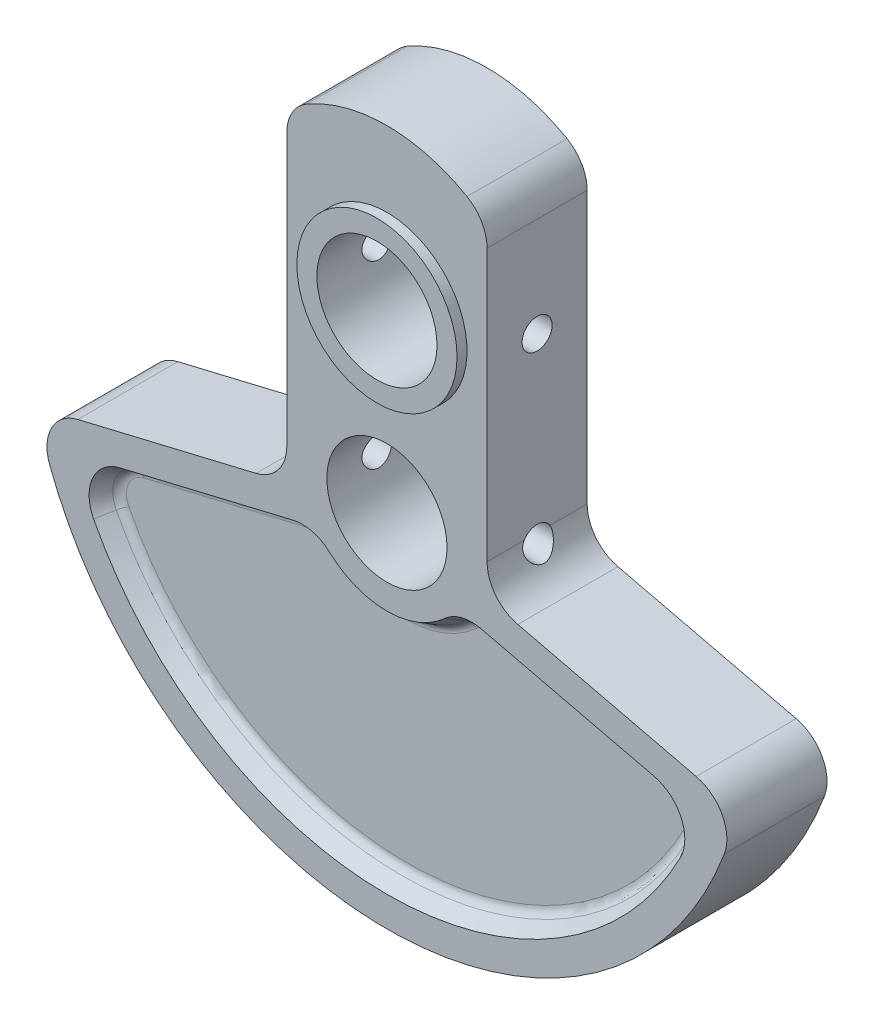
SolidWorks part; units mm, degrees
material "1023 Carbon Steel Sheet (SS)"
ref_plane "Front Plane" through (0, 0, 0) normal (0, 0, 1) x (1, 0, 0)
ref_plane "Top Plane" through (0, 0, 0) normal (0, 1, 0) x (1, 0, 0)
ref_plane "Right Plane" through (0, 0, 0) normal (1, 0, 0) x (0, 0, -1)
sketch "Sketch2" plane through (0, 0, 0) normal (0, 0, 1) x (1, 0, 0)
  line L0 (0, 21.2021) -> (0, -22.0315) construction
  line L1 (-15.4422, -3.6794) -> (-6.5364, -1.5574)
  line L2 (-5, 0.3881) -> (-5, 13.9512)
  line L3 (-5, 15) -> (5, 15) construction
  line L4 (5, 0.3881) -> (5, 13.9512)
  line L5 (15.4422, -3.6794) -> (6.5364, -1.5574)
  arc A0 (-16.851, -6.328) -> (16.851, -6.328) centre (0, 0) ccw
  arc A1 (-16.851, -6.328) -> (-15.4422, -3.6794) centre (-14.9787, -5.6249) cw
  arc A2 (-5, 0.3881) -> (-6.5364, -1.5574) centre (-7, 0.3881) cw
  arc A3 (-4, 15.6832) -> (4, 15.6832) centre (0, 8.755) cw
  arc A4 (-4, 15.6832) -> (-5, 13.9512) centre (-3, 13.9512) ccw
  arc A5 (4, 15.6832) -> (5, 13.9512) centre (3, 13.9512) cw
  arc A6 (5, 0.3881) -> (6.5364, -1.5574) centre (7, 0.3881) ccw
  arc A7 (16.851, -6.328) -> (15.4422, -3.6794) centre (14.9787, -5.6249) ccw
  point P1 (17.5098, -4.172)
  point P11 (-17.5098, -4.172)
  point P16 (0, 0)
  point P21 (0, 15)
  dimension "D1" = 17.5098
  dimension "D3" = 2
  dimension "D2" = 18
  dimension "D6" = 2
  dimension "D7" = 8
  dimension "D8" = 2
  dimension "D4" = 5
  dimension "D5" = 15
extrude "Boss-Extrude1" add sketch "Sketch2" along normal blind 2.5 and the other way blind 2.5
sketch "Sketch3" plane through (0, 0, 2.5) normal (0, 0, 1) x (1, 0, 0)
  line L0 (0, 18.2589) -> (0, -20.5246) construction
  line L1 (-13.3404, -4.7206) -> (-4.6894, -2.6593)
  line L2 (-6.5364, -1.5574) -> (-15.4422, -3.6794) construction
  line L3 (13.3404, -4.7206) -> (4.6894, -2.6593)
  arc A0 (-14.653, -7.5856) -> (14.653, -7.5856) centre (0, 0) ccw
  arc A1 (-16.851, -6.328) -> (16.851, -6.328) centre (0, 0) ccw construction
  arc A2 (-2.8736, -3.1313) -> (2.8736, -3.1313) centre (0, 0) ccw
  arc A3 (-2.8736, -3.1313) -> (-4.6894, -2.6593) centre (-4.2258, -4.6049) ccw
  arc A4 (-14.653, -7.5856) -> (-13.3404, -4.7206) centre (-12.8768, -6.6661) cw
  arc A5 (14.653, -7.5856) -> (13.3404, -4.7206) centre (12.8768, -6.6661) ccw
  arc A6 (2.8736, -3.1313) -> (4.6894, -2.6593) centre (4.2258, -4.6049) cw
  dimension "D1" = 1.5
  dimension "D3" = 8.5
  dimension "D4" = 2
  dimension "D5" = 2
  dimension "D2" = 1.5
extrude "Cut-Extrude1" cut sketch "Sketch3" against normal blind 1 draft 30 contours L1 A3 A2 A6 L3 A5 A0 A4
mirror "Mirror1" about plane through (0, 0, 0) normal (0, 0, 1) of "Cut-Extrude1"
sketch "Sketch4" plane through (0, 0, 2.5) normal (0, 0, 1) x (1, 0, 0)
  circle A0 centre (0, 0) radius 3
  dimension "D1" = 6
extrude "Cut-Extrude3" cut sketch "Sketch4" against normal through all contours A0
sketch "Sketch7" plane through (0, 0, -2.5) normal (0, 0, -1) x (-1, 0, 0)
  circle A0 centre (0, 0) radius 4
  circle A1 centre (0, 0) radius 3
  dimension "D1" = 8
  dimension "D2" = 6
extrude "Boss-Extrude3" add sketch "Sketch7" along normal blind 0.5
sketch "Sketch8" plane through (0, 0, 2.5) normal (0, 0, 1) x (1, 0, 0)
  line L0 (0, 18.5373) -> (0, -20.107) construction
  circle A0 centre (0, 9) radius 3
  dimension "D1" = 6
  dimension "D2" = 9
extrude "Cut-Extrude4" cut sketch "Sketch8" against normal through all
sketch "Sketch9" plane through (0, 0, 2.5) normal (0, 0, 1) x (1, 0, 0)
  circle A0 centre (0, 9) radius 4
  circle A1 centre (0, 9) radius 3
  dimension "D1" = 8
  dimension "D2" = 6
extrude "Boss-Extrude4" add sketch "Sketch9" along normal blind 0.5
sketch "Sketch10" plane through (-5, 0, 0) normal (-1, 0, 0) x (0, 0, 1)
  line L0 (0, 18.0734) -> (0, -19.272) construction
  circle A0 centre (0, 9) radius 0.75
  circle A1 centre (0, 0) radius 0.75
  dimension "D1" = 1.5
  dimension "D2" = 1.5
  dimension "D3" = 9
extrude "Cut-Extrude5" cut sketch "Sketch10" against normal through all and the other way through all
fillet "Fillet1" radius 0.5 8 edges at (-14.1702, -6.0736, 1.5) (-8.8811, -4.2516, 1.5) (-3.868, -3.228, 1.5) (0, -4.8274, 1.5) (3.868, -3.228, 1.5) (8.8811, -4.2516, 1.5) (14.1702, -6.0736, 1.5) (0, -15.9226, 1.5) type face fillet first side face at (0, -5.982, 1.5) second side face at (14.1339, -6.0902, 2) second side face at (8.948, -3.9708, 2) second side face at (3.8205, -3.0453, 2) second side face at (0, -3.9413, 2) second side face at (-3.8205, -3.0453, 2) second side face at (0, -11.8321, 2) second side face at (-14.1339, -6.0902, 2) second side face at (-8.948, -3.9708, 2)
fillet "Fillet2" radius 0.5 1 edges at (0, -4.8274, -1.5) type face fillet first side face at (0, -5.982, -1.5) second side face at (0, -3.9413, -2)
